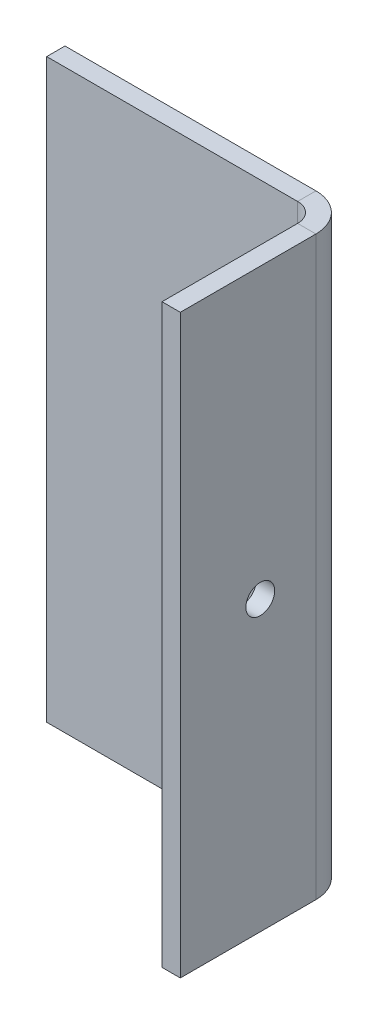
SolidWorks part; units mm, degrees
note: The reader was unsure of these and kept them because the rebuilt part matched: flange length of "Edge-Flange1".
ref_plane "Front Plane" through (0, 0, 0) normal (0, 0, 1) x (1, 0, 0)
ref_plane "Top Plane" through (0, 0, 0) normal (0, 1, 0) x (1, 0, 0)
ref_plane "Right Plane" through (0, 0, 0) normal (1, 0, 0) x (0, 0, -1)
sketch "Sketch1" plane through (0, 0, 0) normal (0, 0, 1) x (1, 0, 0)
  line L1 (-25, 50) -> (25, 50)
  line L2 (-25, 50) -> (-25, -50)
  line L3 (-25, -50) -> (25, -50)
  line L4 (25, 50) -> (25, -50)
  point P4 (-25, 0)
  point P6 (0, 50)
  dimension "D1" = 100
  dimension "D2" = 50
base flange "Base-Flange2" sketch "Sketch1" thickness 3.175 reverse thickness direction no parameters "D1"=0.7366
edge flange "Edge-Flange1" sketch "Sketch12" flange angle 90 flange length 30 flange position material inside bend radius 3.302 thickness 3.175 relief rectangular parameters "D6"=10
sketch "Sketch12" plane through (25, 0, 0) normal (1, 0, 0) x (0, 1, 0)
  line L0 (-50, 0) -> (50, 0) construction
  line L1 (-50, 0) -> (50, 0)
  line L2 (-50, 0) -> (-50, 26.825)
  line L3 (-50, 26.825) -> (50, 26.825)
  line L4 (50, 26.825) -> (50, 0)
bend "EdgeBend1" bend radius 3.302 bend angle 90 parameters "D5"=1
sketch "Sketch13" plane through (25, 0, 0) normal (1, 0, 0) x (0, 0, -1)
  line L0 (3.175, 0) -> (-26.825, 0) construction
  line L1 (3.175, 50) -> (3.175, -50) construction
  line L2 (-26.825, 50) -> (-26.825, -50) construction
  line L3 (-3.302, 50) -> (-3.302, -50) construction
  point P0 (-12.954, 0)
  dimension "D1" = 9.652
hole_wizard "Ø5.0mm Dowel Hole1" positions "Sketch20" profile "Sketch21" hole size "Ø5.0" standard "BSI" end condition up to next
sketch "Sketch20" plane through (25, 0, 0) normal (1, 0, 0) x (0, 0, -1)
  point P0 (-12.954, 0)
sketch "Sketch21" plane through (25, 0, 12.954) normal (0, 1, 0) x (0, 0, -1)
  line L0 (0, 0) -> (0, 3.175)
  line L1 (0, 3.175) -> (2.5, 3.175)
  line L2 (2.5, 3.175) -> (2.5, 0)
  line L5 (2.5, 0) -> (0, 0)
  line L11 (0, -6.35) -> (0, 107.95) construction
  dimension "Thru Hole Dia." = 5
  dimension "Thru Hole Depth" = 3.175
sketch "Bend-Lines3" [suppressed] plane through (0, 0, 0) normal (0, 1, 0) x (1, 0, 0)
sketch "Bounding-Box3" [suppressed] plane through (0, 0, 0) normal (0, 1, 0) x (1, 0, 0)
sheet metal parameters "Sheet-Metal2" thickness 3.175 parameters "D1"=0.7366
flat pattern "Flat-Pattern2" [suppressed]
sketch "Bend-Lines4" plane through (0, 0, 0) normal (0, 1, 0) x (1, 0, 0)
sketch3d "Bounding-Box4" [suppressed]
  line L0 (-25, 50, 0) -> (-25, -50, 0) construction
  line L1 (25, 50, 0) -> (25, -50, 0) construction
  line L2 (-25, 50, 0) -> (25, 50, 0) construction
  line L3 (-25, -50, 0) -> (25, -50, 0) construction
sheet metal parameters "Sheet-Metal3" thickness 3.175 parameters "D1"=0.7366
flat pattern "Flat-Pattern2"
sketch "Bend-Lines4" plane through (0, 0, 0) normal (0, 0, 1) x (1, 0, 0)
  line L0 (22.3632, -50) -> (22.3632, 50) construction
  line L1 (22.3632, -50) -> (22.3632, 50) construction
sketch3d "Bounding-Box4" [suppressed]
  line L0 (49.7264, 50, 0) -> (49.7264, -50, 0) construction
  line L1 (-25, 50, 0) -> (-25, -50, 0) construction
  line L2 (49.7264, 50, 0) -> (-25, 50, 0) construction
  line L3 (49.7264, -50, 0) -> (-25, -50, 0) construction
bend of the flat pattern "Flatten-<EdgeBend1>1"
sheet metal parameters "Sheet-Metal6" thickness 3.175 parameters "D1"=0.7366
flat pattern "Flat-Pattern2" [suppressed]
sketch "Bend-Lines4" plane through (0, 0, 0) normal (0, 0, 1) x (1, 0, 0)
  line L0 (22.3632, -50) -> (22.3632, 50) construction
  line L1 (22.3632, -50) -> (22.3632, 50) construction
sketch3d "Bounding-Box4" [suppressed]
  line L0 (49.7264, 50, 0) -> (49.7264, -50, 0) construction
  line L1 (-25, 50, 0) -> (-25, -50, 0) construction
  line L2 (49.7264, 50, 0) -> (-25, 50, 0) construction
  line L3 (49.7264, -50, 0) -> (-25, -50, 0) construction
bend of the flat pattern "Flatten-<EdgeBend1>1"
sketch "Sketch13-1" plane through (22.9014, 0, -3.175) normal (0, 0, -1) x (-1, 0, 0)
  line L0 (3.175, 0) -> (-26.825, 0) construction
  line L3 (-3.302, 50) -> (-3.302, -50) construction
  point P0 (-12.954, 0)
  dimension "D1" = 9.652
